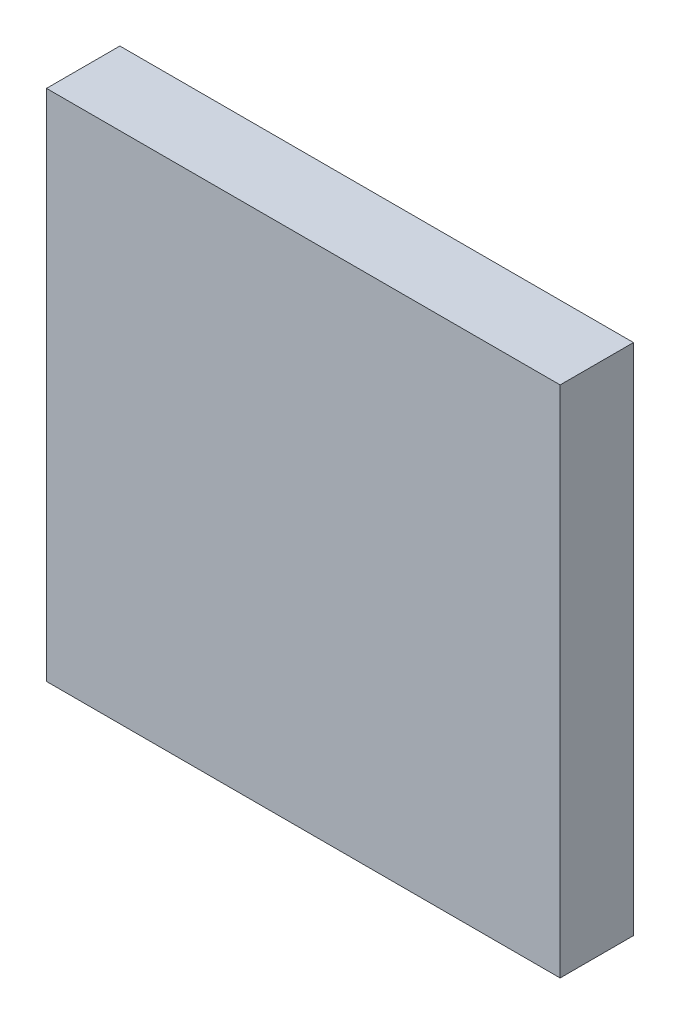
SolidWorks part; units mm, degrees
ref_plane "Спереди" through (0, 0, 0) normal (0, 0, 1) x (1, 0, 0)
ref_plane "Сверху" through (0, 0, 0) normal (0, 1, 0) x (1, 0, 0)
ref_plane "Справа" through (0, 0, 0) normal (1, 0, 0) x (0, 0, -1)
sketch "Эскиз5" plane through (0, 0, 0) normal (0, 0, 1) x (1, 0, 0)
  line L1 (-35, -35) -> (35, -35)
  line L2 (-35, -35) -> (-35, 35)
  line L3 (-35, 35) -> (35, 35)
  line L4 (35, -35) -> (35, 35)
  line L5 (-35, -35) -> (35, 35) construction
  line L6 (-35, 35) -> (35, -35) construction
  point P0 (0, 0)
extrude "Бобышка-Вытянуть2" add sketch "Эскиз5" along normal blind 10 contours L2 L3 L4 L1
sketch "Эскиз9" plane through (0, 0, 10) normal (0, 0, 1) x (1, 0, 0)
  line L0 (-15.9693, -2.4457) -> (-15.2752, -2.3914)
  line L1 (-14.1689, -1.194) -> (-14.17, 0.0011)
  line L2 (-15.1833, 1.1854) -> (-16.1735, 1.3414)
  line L3 (-7.5117, 15.2981) -> (-6.354, 13.3333)
  line L4 (-4.52, 14.0613) -> (-5.009, 16.2935)
  line L5 (5.8666, 15.0526) -> (5.5666, 14.4244)
  line L6 (6.0505, 12.8676) -> (7.0859, 12.271)
  line L7 (8.6182, 12.5564) -> (9.2484, 13.336)
  line L8 (16.9601, -1.13) -> (14.724, -1.1639)
  line L9 (14.4375, -3.1163) -> (16.5652, -3.7935)
  line L10 (10.1027, -12.6069) -> (9.7086, -12.0331)
  line L11 (8.1185, -11.6737) -> (7.0841, -12.2721)
  line L12 (6.5651, -13.7418) -> (6.9251, -14.6773)
  line L13 (-9.4469, -14.0923) -> (-8.37, -12.1694)
  line L14 (-9.9175, -10.9451) -> (-11.5447, -12.4356)
  line L15 (-30, -30) -> (30, -30)
  line L16 (30, -30) -> (30, 30)
  line L17 (30, 30) -> (-30, 30)
  line L18 (-30, 30) -> (-30, -30)
  ellipse E0 centre (-0.0001, 0.0435) end of major axis (-0.0001, 12.5436) minor radius 12.5001
  spline S0 degree 3 poles (3, -26) (3, -24.3431) (1.6569, -23) (0, -23) knots 0 0 0 0 0.2 0.2 0.2 0.2
  spline S1 degree 3 poles (0, -23) (-1.6568, -23) (-3, -24.3431) (-3, -26) knots 0.2 0.2 0.2 0.2 0.4 0.4 0.4 0.4
  spline S2 degree 3 poles (-3, -26) (-3, -27.6568) (-1.6569, -29) (0, -29) knots 0.4 0.4 0.4 0.4 0.6 0.6 0.6 0.6
  spline S3 degree 3 poles (0, -29) (1.6568, -29) (3, -27.6569) (3, -26) knots 0.6 0.6 0.6 0.6 1 1 1 1
  spline S4 degree 3 poles (-23, 0) (-23, 1.6569) (-24.3431, 3) (-26, 3) knots 0 0 0 0 0.2 0.2 0.2 0.2
  spline S5 degree 3 poles (-26, 3) (-27.6568, 3) (-29, 1.6569) (-29, 0) knots 0.2 0.2 0.2 0.2 0.4 0.4 0.4 0.4
  spline S6 degree 3 poles (-29, 0) (-29, -1.6568) (-27.6569, -3) (-26, -3) knots 0.4 0.4 0.4 0.4 0.6 0.6 0.6 0.6
  spline S7 degree 3 poles (-26, -3) (-24.3432, -3) (-23, -1.6569) (-23, 0) knots 0.6 0.6 0.6 0.6 1 1 1 1
  spline S8 degree 3 poles (29, 0) (29, 1.6569) (27.6569, 3) (26, 3) knots 0 0 0 0 0.2 0.2 0.2 0.2
  spline S9 degree 3 poles (26, 3) (24.3432, 3) (23, 1.6569) (23, 0) knots 0.2 0.2 0.2 0.2 0.4 0.4 0.4 0.4
  spline S10 degree 3 poles (23, 0) (23, -1.6568) (24.3431, -3) (26, -3) knots 0.4 0.4 0.4 0.4 0.6 0.6 0.6 0.6
  spline S11 degree 3 poles (26, -3) (27.6568, -3) (29, -1.6569) (29, 0) knots 0.6 0.6 0.6 0.6 1 1 1 1
  spline S12 degree 3 poles (3, 26) (3, 27.6569) (1.6569, 29) (0, 29) knots 0 0 0 0 0.2 0.2 0.2 0.2
  spline S13 degree 3 poles (0, 29) (-1.6568, 29) (-3, 27.6569) (-3, 26) knots 0.2 0.2 0.2 0.2 0.4 0.4 0.4 0.4
  spline S14 degree 3 poles (-3, 26) (-3, 24.3432) (-1.6569, 23) (0, 23) knots 0.4 0.4 0.4 0.4 0.6 0.6 0.6 0.6
  spline S15 degree 3 poles (0, 23) (1.6568, 23) (3, 24.3431) (3, 26) knots 0.6 0.6 0.6 0.6 1 1 1 1
  spline S16 degree 3 poles (-16.7485, -2.8866) (-16.7849, -2.7489) (-16.7119, -2.6575) (-16.5914, -2.5899) knots 0 0 0 0 0.021277 0.021277 0.021277 0.021277
  spline S17 degree 3 poles (-16.5914, -2.5899) (-16.4679, -2.5206) (-16.1105, -2.4568) (-15.9693, -2.4457) knots 0.021277 0.021277 0.021277 0.021277 0.042553 0.042553 0.042553 0.042553
  spline S18 degree 3 poles (-15.2752, -2.3914) (-14.6503, -2.3424) (-14.1684, -1.8208) (-14.1689, -1.194) knots 0.06383 0.06383 0.06383 0.06383 0.085106 0.085106 0.085106 0.085106
  spline S19 degree 3 poles (-14.17, 0.0011) (-14.1705, 0.5913) (-14.6002, 1.0936) (-15.1833, 1.1854) knots 0.106383 0.106383 0.106383 0.106383 0.12766 0.12766 0.12766 0.12766
  spline S20 degree 3 poles (-16.1735, 1.3414) (-16.4381, 1.383) (-16.9337, 1.6001) (-16.9034, 1.8662) knots 0.148936 0.148936 0.148936 0.148936 0.170213 0.170213 0.170213 0.170213
  spline S21 degree 3 poles (-16.9034, 1.8662) (-16.2735, 7.7755) (-12.6158, 12.7801) (-7.5117, 15.2981) knots 0.170213 0.170213 0.170213 0.170213 0.191489 0.191489 0.191489 0.191489
  spline S22 degree 3 poles (-6.354, 13.3333) (-6.1017, 12.914) (-5.5831, 12.7389) (-5.1282, 12.9194) knots 0.212766 0.212766 0.212766 0.212766 0.234043 0.234043 0.234043 0.234043
  spline S23 degree 3 poles (-5.1282, 12.9194) (-4.6734, 13.1) (-4.416, 13.5832) (-4.52, 14.0613) knots 0.234043 0.234043 0.234043 0.234043 0.255319 0.255319 0.255319 0.255319
  spline S24 degree 3 poles (-5.009, 16.2935) (-3.4256, 16.781) (-1.7434, 17.0434) (0, 17.0434) knots 0.276596 0.276596 0.276596 0.276596 0.297872 0.297872 0.297872 0.297872
  spline S25 degree 3 poles (0, 17.0434) (2.06, 17.0434) (4.0345, 16.6769) (5.8617, 16.0058) knots 0.297872 0.297872 0.297872 0.297872 0.319149 0.319149 0.319149 0.319149
  spline S26 degree 3 poles (5.8617, 16.0058) (5.9953, 15.9584) (6.0613, 15.8415) (6.1155, 15.7106) knots 0.319149 0.319149 0.319149 0.319149 0.340426 0.340426 0.340426 0.340426
  spline S27 degree 3 poles (6.1155, 15.7106) (6.1697, 15.5797) (5.9276, 15.1805) (5.8666, 15.0526) knots 0.340426 0.340426 0.340426 0.340426 0.361702 0.361702 0.361702 0.361702
  spline S28 degree 3 poles (5.5666, 14.4244) (5.2966, 13.8588) (5.5074, 13.1805) (6.0505, 12.8676) knots 0.382979 0.382979 0.382979 0.382979 0.404255 0.404255 0.404255 0.404255
  spline S29 degree 3 poles (7.0859, 12.271) (7.5974, 11.9764) (8.2472, 12.0974) (8.6182, 12.5564) knots 0.425532 0.425532 0.425532 0.425532 0.446809 0.446809 0.446809 0.446809
  spline S30 degree 3 poles (9.2484, 13.336) (9.4155, 13.5426) (9.7733, 13.9496) (9.9892, 13.8005) knots 0.468085 0.468085 0.468085 0.468085 0.489362 0.489362 0.489362 0.489362
  spline S31 degree 3 poles (9.9892, 13.8005) (9.9897, 13.8002) (9.9901, 13.7998) (9.9906, 13.7995) knots 0.489362 0.489362 0.489362 0.489362 0.510638 0.510638 0.510638 0.510638
  spline S32 degree 3 poles (9.9906, 13.7995) (14.2385, 10.7091) (17, 5.6988) (17, 0.0434) knots 0.510638 0.510638 0.510638 0.510638 0.531915 0.531915 0.531915 0.531915
  spline S33 degree 3 poles (17, 0.0434) (17, -0.351) (16.9865, -0.7423) (16.9601, -1.13) knots 0.531915 0.531915 0.531915 0.531915 0.553191 0.553191 0.553191 0.553191
  spline S34 degree 3 poles (14.724, -1.1639) (14.2347, -1.1728) (13.8237, -1.5344) (13.7527, -2.0186) knots 0.574468 0.574468 0.574468 0.574468 0.595745 0.595745 0.595745 0.595745
  spline S35 degree 3 poles (13.7527, -2.0186) (13.6816, -2.5027) (13.9714, -2.9672) (14.4375, -3.1163) knots 0.595745 0.595745 0.595745 0.595745 0.617021 0.617021 0.617021 0.617021
  spline S36 degree 3 poles (16.5652, -3.7935) (15.7442, -7.3523) (13.8058, -10.484) (11.1395, -12.7989) knots 0.638298 0.638298 0.638298 0.638298 0.659574 0.659574 0.659574 0.659574
  spline S37 degree 3 poles (11.1395, -12.7989) (11.0317, -12.8908) (10.5897, -12.8381) (10.4494, -12.8196) knots 0.659574 0.659574 0.659574 0.659574 0.680851 0.680851 0.680851 0.680851
  spline S38 degree 3 poles (10.4494, -12.8196) (10.3089, -12.8011) (10.1829, -12.7237) (10.1027, -12.6069) knots 0.680851 0.680851 0.680851 0.680851 0.702128 0.702128 0.702128 0.702128
  spline S39 degree 3 poles (9.7086, -12.0331) (9.3538, -11.5163) (8.661, -11.3598) (8.1185, -11.6737) knots 0.723404 0.723404 0.723404 0.723404 0.744681 0.744681 0.744681 0.744681
  spline S40 degree 3 poles (7.0841, -12.2721) (6.5732, -12.5677) (6.3531, -13.1909) (6.5651, -13.7418) knots 0.765957 0.765957 0.765957 0.765957 0.787234 0.787234 0.787234 0.787234
  spline S41 degree 3 poles (6.9251, -14.6773) (7.021, -14.9265) (6.922, -15.4856) (6.6778, -15.5949) knots 0.808511 0.808511 0.808511 0.808511 0.829787 0.829787 0.829787 0.829787
  spline S42 degree 3 poles (6.6778, -15.5949) (4.6278, -16.4714) (2.3705, -16.9566) (0, -16.9566) knots 0.829787 0.829787 0.829787 0.829787 0.851064 0.851064 0.851064 0.851064
  spline S43 degree 3 poles (0, -16.9566) (-3.4958, -16.9566) (-6.7452, -15.9014) (-9.4469, -14.0923) knots 0.851064 0.851064 0.851064 0.851064 0.87234 0.87234 0.87234 0.87234
  spline S44 degree 3 poles (-8.37, -12.1694) (-8.133, -11.7413) (-8.2407, -11.2045) (-8.6244, -10.9009) knots 0.893617 0.893617 0.893617 0.893617 0.914894 0.914894 0.914894 0.914894
  spline S45 degree 3 poles (-8.6244, -10.9009) (-9.0082, -10.5972) (-9.5554, -10.6159) (-9.9175, -10.9451) knots 0.914894 0.914894 0.914894 0.914894 0.93617 0.93617 0.93617 0.93617
  spline S46 degree 3 poles (-11.5447, -12.4356) (-14.22, -9.9595) (-16.0977, -6.6335) (-16.7485, -2.8866) knots 0.957447 0.957447 0.957447 0.957447 1 1 1 1
sketch "Эскиз13" plane through (0, 0, 10) normal (0, 0, 1) x (1, 0, 0)
  line L0 (-8.5, 3.8388) -> (-8.5, -2.9703)
  line L1 (8.5, -2.9278) -> (8.5, 3.8388)
  spline S0 degree 3 poles (-3.7602, -6.2881) (-4.1456, -5.7125) (-4.7609, -5.3316) (-5.448, -5.2431) knots 0 0 0 0 0.333333 0.333333 0.333333 0.333333
  spline S1 degree 3 poles (-5.448, -5.2431) (-6.135, -5.1547) (-6.8268, -5.3675) (-7.3454, -5.8267) knots 0.333333 0.333333 0.333333 0.333333 1 1 1 1
  spline S2 degree 3 poles (-8.2703, 4.2595) (-8.4134, 4.1675) (-8.5, 4.009) (-8.5, 3.8388) knots 0 0 0 0 1 1 1 1
  spline S3 degree 3 poles (8.2703, 4.2595) (3.2319, 7.4966) (-3.2319, 7.4966) (-8.2703, 4.2595) knots 0 0 0 0 1 1 1 1
  spline S4 degree 3 poles (8.5, 3.8388) (8.5, 4.009) (8.4134, 4.1675) (8.2703, 4.2595) knots 0 0 0 0 1 1 1 1
  spline S5 degree 3 poles (-8.9672, -4.0581) (-8.6689, -3.7749) (-8.5, -3.3816) (-8.5, -2.9703) knots 0 0 0 0 1 1 1 1
  spline S6 degree 3 poles (-8.9672, -4.0581) (-9.4419, -4.5088) (-9.4678, -5.2568) (-9.0253, -5.7393) knots 0 0 0 0 0.333333 0.333333 0.333333 0.333333
  spline S7 degree 3 poles (-9.0253, -5.7393) (-8.5829, -6.2218) (-7.8355, -6.2607) (-7.3454, -5.8267) knots 0.333333 0.333333 0.333333 0.333333 1 1 1 1
  spline S8 degree 3 poles (8.5, -2.9278) (8.5, -3.3579) (8.6732, -3.77) (8.9805, -4.0709) knots 0 0 0 0 1 1 1 1
  spline S9 degree 3 poles (7.6987, -6.0438) (6.4648, -5.5547) (5.0779, -5.6352) (3.9089, -6.2639) knots 0 0 0 0 1 1 1 1
  spline S10 degree 3 poles (7.6987, -6.0438) (8.2299, -6.2544) (8.8358, -6.0612) (9.1472, -5.5821) knots 0 0 0 0 0.333333 0.333333 0.333333 0.333333
  spline S11 degree 3 poles (9.1472, -5.5821) (9.4585, -5.1029) (9.3888, -4.4707) (8.9805, -4.0709) knots 0.333333 0.333333 0.333333 0.333333 1 1 1 1
  spline S12 degree 3 poles (3.1792, -6.3186) (1.2825, -5.6394) (-0.8063, -5.741) (-2.6281, -6.6012) knots 0 0 0 0 1 1 1 1
  spline S13 degree 3 poles (-3.7602, -6.2881) (-3.5123, -6.6582) (-3.0309, -6.7914) (-2.6281, -6.6012) knots 0 0 0 0 1 1 1 1
  spline S14 degree 3 poles (3.1792, -6.3186) (3.4192, -6.4045) (3.6844, -6.3847) (3.9089, -6.2639) knots 0 0 0 0 1 1 1 1
sketch "Эскиз15" plane through (0, 0, 10) normal (0, 0, 1) x (1, 0, 0)
  line L0 (-8.5, 3.8389) -> (-8.5, -2.9702)
  line L1 (8.5, -2.9277) -> (8.5, 3.8389)
  line L2 (-12.5, -12.5) -> (12.5, -12.5)
  line L3 (12.5, -12.5) -> (12.5, 12.5)
  line L4 (12.5, 12.5) -> (-12.5, 12.5)
  line L5 (-12.5, 12.5) -> (-12.5, -12.5)
  spline S0 degree 3 poles (8, 2.6874) (8, 2.9636) (7.7761, 3.1874) (7.5, 3.1874) knots 0 0 0 0 0.2 0.2 0.2 0.2
  spline S1 degree 3 poles (7.5, 3.1874) (7.2239, 3.1874) (7, 2.9636) (7, 2.6874) knots 0.2 0.2 0.2 0.2 0.4 0.4 0.4 0.4
  spline S2 degree 3 poles (7, 2.6874) (7, 2.4113) (7.2239, 2.1874) (7.5, 2.1874) knots 0.4 0.4 0.4 0.4 0.6 0.6 0.6 0.6
  spline S3 degree 3 poles (7.5, 2.1874) (7.7761, 2.1874) (8, 2.4113) (8, 2.6874) knots 0.6 0.6 0.6 0.6 1 1 1 1
  spline S4 degree 3 poles (-4.6079, 1.1218) (-4.6079, 1.6188) (-5.0108, 2.0218) (-5.5079, 2.0218) knots 0 0 0 0 0.2 0.2 0.2 0.2
  spline S5 degree 3 poles (-5.5079, 2.0218) (-6.0049, 2.0218) (-6.4079, 1.6188) (-6.4079, 1.1218) knots 0.2 0.2 0.2 0.2 0.4 0.4 0.4 0.4
  spline S6 degree 3 poles (-6.4079, 1.1218) (-6.4079, 0.6247) (-6.0049, 0.2218) (-5.5079, 0.2218) knots 0.4 0.4 0.4 0.4 0.6 0.6 0.6 0.6
  spline S7 degree 3 poles (-5.5079, 0.2218) (-5.0108, 0.2218) (-4.6079, 0.6247) (-4.6079, 1.1218) knots 0.6 0.6 0.6 0.6 1 1 1 1
  spline S8 degree 3 poles (7.0549, -0.2908) (7.0549, 0.2063) (6.652, 0.6092) (6.1549, 0.6092) knots 0 0 0 0 0.2 0.2 0.2 0.2
  spline S9 degree 3 poles (6.1549, 0.6092) (5.6579, 0.6092) (5.2549, 0.2063) (5.2549, -0.2908) knots 0.2 0.2 0.2 0.2 0.4 0.4 0.4 0.4
  spline S10 degree 3 poles (5.2549, -0.2908) (5.2549, -0.7878) (5.6579, -1.1908) (6.1549, -1.1908) knots 0.4 0.4 0.4 0.4 0.6 0.6 0.6 0.6
  spline S11 degree 3 poles (6.1549, -1.1908) (6.652, -1.1908) (7.0549, -0.7878) (7.0549, -0.2908) knots 0.6 0.6 0.6 0.6 1 1 1 1
  spline S12 degree 3 poles (-7, 2.6874) (-7, 2.9636) (-7.2239, 3.1874) (-7.5, 3.1874) knots 0 0 0 0 0.2 0.2 0.2 0.2
  spline S13 degree 3 poles (-7.5, 3.1874) (-7.7761, 3.1874) (-8, 2.9636) (-8, 2.6874) knots 0.2 0.2 0.2 0.2 0.4 0.4 0.4 0.4
  spline S14 degree 3 poles (-8, 2.6874) (-8, 2.4113) (-7.7761, 2.1874) (-7.5, 2.1874) knots 0.4 0.4 0.4 0.4 0.6 0.6 0.6 0.6
  spline S15 degree 3 poles (-7.5, 2.1874) (-7.2239, 2.1874) (-7, 2.4113) (-7, 2.6874) knots 0.6 0.6 0.6 0.6 1 1 1 1
  spline S16 degree 3 poles (-7.5909, -4.9282) (-7.5909, -4.6244) (-7.8371, -4.3782) (-8.1409, -4.3782) knots 0 0 0 0 0.2 0.2 0.2 0.2
  spline S17 degree 3 poles (-8.1409, -4.3782) (-8.4447, -4.3782) (-8.6909, -4.6244) (-8.6909, -4.9282) knots 0.2 0.2 0.2 0.2 0.4 0.4 0.4 0.4
  spline S18 degree 3 poles (-8.6909, -4.9282) (-8.6909, -5.2319) (-8.4447, -5.4782) (-8.1409, -5.4782) knots 0.4 0.4 0.4 0.4 0.6 0.6 0.6 0.6
  spline S19 degree 3 poles (-8.1409, -5.4782) (-7.8371, -5.4782) (-7.5909, -5.2319) (-7.5909, -4.9282) knots 0.6 0.6 0.6 0.6 1 1 1 1
  spline S20 degree 3 poles (8.6909, -4.9282) (8.6909, -4.6244) (8.4447, -4.3782) (8.1409, -4.3782) knots 0 0 0 0 0.2 0.2 0.2 0.2
  spline S21 degree 3 poles (8.1409, -4.3782) (7.8371, -4.3782) (7.5909, -4.6244) (7.5909, -4.9282) knots 0.2 0.2 0.2 0.2 0.4 0.4 0.4 0.4
  spline S22 degree 3 poles (7.5909, -4.9282) (7.5909, -5.2319) (7.8371, -5.4782) (8.1409, -5.4782) knots 0.4 0.4 0.4 0.4 0.6 0.6 0.6 0.6
  spline S23 degree 3 poles (8.1409, -5.4782) (8.4447, -5.4782) (8.6909, -5.2319) (8.6909, -4.9282) knots 0.6 0.6 0.6 0.6 1 1 1 1
  spline S24 degree 3 poles (3.9826, -5.4712) (3.9826, -5.195) (3.7587, -4.9712) (3.4826, -4.9712) knots 0 0 0 0 0.2 0.2 0.2 0.2
  spline S25 degree 3 poles (3.4826, -4.9712) (3.2064, -4.9712) (2.9826, -5.195) (2.9826, -5.4712) knots 0.2 0.2 0.2 0.2 0.4 0.4 0.4 0.4
  spline S26 degree 3 poles (2.9826, -5.4712) (2.9826, -5.7473) (3.2064, -5.9712) (3.4826, -5.9712) knots 0.4 0.4 0.4 0.4 0.6 0.6 0.6 0.6
  spline S27 degree 3 poles (3.4826, -5.9712) (3.7587, -5.9712) (3.9826, -5.7473) (3.9826, -5.4712) knots 0.6 0.6 0.6 0.6 1 1 1 1
  spline S28 degree 3 poles (-2.5123, -5.7872) (-2.5123, -5.5111) (-2.7362, -5.2872) (-3.0123, -5.2872) knots 0 0 0 0 0.2 0.2 0.2 0.2
  spline S29 degree 3 poles (-3.0123, -5.2872) (-3.2885, -5.2872) (-3.5123, -5.5111) (-3.5123, -5.7872) knots 0.2 0.2 0.2 0.2 0.4 0.4 0.4 0.4
  spline S30 degree 3 poles (-3.5123, -5.7872) (-3.5123, -6.0634) (-3.2885, -6.2872) (-3.0123, -6.2872) knots 0.4 0.4 0.4 0.4 0.6 0.6 0.6 0.6
  spline S31 degree 3 poles (-3.0123, -6.2872) (-2.7362, -6.2872) (-2.5123, -6.0634) (-2.5123, -5.7872) knots 0.6 0.6 0.6 0.6 1 1 1 1
  spline S32 degree 3 poles (6.6049, -0.2908) (6.6049, -0.0422) (6.4034, 0.1592) (6.1549, 0.1592) knots 0 0 0 0 0.2 0.2 0.2 0.2
  spline S33 degree 3 poles (6.1549, 0.1592) (5.9064, 0.1592) (5.7049, -0.0422) (5.7049, -0.2908) knots 0.2 0.2 0.2 0.2 0.4 0.4 0.4 0.4
  spline S34 degree 3 poles (5.7049, -0.2908) (5.7049, -0.5393) (5.9064, -0.7408) (6.1549, -0.7408) knots 0.4 0.4 0.4 0.4 0.6 0.6 0.6 0.6
  spline S35 degree 3 poles (6.1549, -0.7408) (6.4034, -0.7408) (6.6049, -0.5393) (6.6049, -0.2908) knots 0.6 0.6 0.6 0.6 1 1 1 1
  spline S36 degree 3 poles (-5.0579, 1.1218) (-5.0579, 1.3703) (-5.2594, 1.5718) (-5.5079, 1.5718) knots 0 0 0 0 0.2 0.2 0.2 0.2
  spline S37 degree 3 poles (-5.5079, 1.5718) (-5.7564, 1.5718) (-5.9579, 1.3703) (-5.9579, 1.1218) knots 0.2 0.2 0.2 0.2 0.4 0.4 0.4 0.4
  spline S38 degree 3 poles (-5.9579, 1.1218) (-5.9579, 0.8733) (-5.7564, 0.6718) (-5.5079, 0.6718) knots 0.4 0.4 0.4 0.4 0.6 0.6 0.6 0.6
  spline S39 degree 3 poles (-5.5079, 0.6718) (-5.2594, 0.6718) (-5.0579, 0.8733) (-5.0579, 1.1218) knots 0.6 0.6 0.6 0.6 1 1 1 1
  spline S40 degree 3 poles (5.7898, -5.6368) (5.8728, -5.6949) (5.9715, -5.7264) (6.0728, -5.7271) knots 0 0 0 0 1 1 1 1
  spline S41 degree 3 poles (-5.4083, -5.2485) (-5.2964, -5.2648) (-5.1822, -5.2427) (-5.0845, -5.1857) knots 0 0 0 0 1 1 1 1
  spline S42 degree 3 poles (-3.7602, -6.288) (-4.1456, -5.7124) (-4.7609, -5.3315) (-5.448, -5.243) knots 0 0 0 0 0.333333 0.333333 0.333333 0.333333
  spline S43 degree 3 poles (-5.448, -5.243) (-6.135, -5.1546) (-6.8268, -5.3674) (-7.3454, -5.8266) knots 0.333333 0.333333 0.333333 0.333333 1 1 1 1
  spline S44 degree 3 poles (-8.2703, 4.2596) (-8.4134, 4.1676) (-8.5, 4.0091) (-8.5, 3.8389) knots 0 0 0 0 1 1 1 1
  spline S45 degree 3 poles (8.2703, 4.2596) (3.2319, 7.4967) (-3.2319, 7.4967) (-8.2703, 4.2596) knots 0 0 0 0 1 1 1 1
  spline S46 degree 3 poles (8.5, 3.8389) (8.5, 4.0091) (8.4134, 4.1676) (8.2703, 4.2596) knots 0 0 0 0 1 1 1 1
  spline S47 degree 3 poles (5.7898, -5.6368) (2.563, -3.3793) (-1.6818, -3.2032) (-5.0845, -5.1857) knots 0 0 0 0 1 1 1 1
  spline S48 degree 3 poles (-8.9672, -4.058) (-8.6689, -3.7748) (-8.5, -3.3815) (-8.5, -2.9702) knots 0 0 0 0 1 1 1 1
  spline S49 degree 3 poles (-8.9672, -4.058) (-9.4419, -4.5087) (-9.4678, -5.2567) (-9.0253, -5.7392) knots 0 0 0 0 0.333333 0.333333 0.333333 0.333333
  spline S50 degree 3 poles (-9.0253, -5.7392) (-8.5829, -6.2217) (-7.8355, -6.2606) (-7.3454, -5.8266) knots 0.333333 0.333333 0.333333 0.333333 1 1 1 1
  spline S51 degree 3 poles (8.5, -2.9277) (8.5, -3.3578) (8.6732, -3.7699) (8.9805, -4.0708) knots 0 0 0 0 1 1 1 1
  spline S52 degree 3 poles (7.6987, -6.0437) (6.4648, -5.5546) (5.0779, -5.6351) (3.9089, -6.2638) knots 0 0 0 0 1 1 1 1
  spline S53 degree 3 poles (7.6987, -6.0437) (8.2299, -6.2543) (8.8358, -6.0611) (9.1472, -5.582) knots 0 0 0 0 0.333333 0.333333 0.333333 0.333333
  spline S54 degree 3 poles (9.1472, -5.582) (9.4585, -5.1028) (9.3888, -4.4706) (8.9805, -4.0708) knots 0.333333 0.333333 0.333333 0.333333 1 1 1 1
  spline S55 degree 3 poles (3.1792, -6.3185) (1.2825, -5.6393) (-0.8063, -5.7409) (-2.6281, -6.6011) knots 0 0 0 0 1 1 1 1
  spline S56 degree 3 poles (-3.7602, -6.288) (-3.5123, -6.6581) (-3.0309, -6.7913) (-2.6281, -6.6011) knots 0 0 0 0 1 1 1 1
  spline S57 degree 3 poles (3.1792, -6.3185) (3.4192, -6.4044) (3.6844, -6.3846) (3.9089, -6.2638) knots 0 0 0 0 1 1 1 1
sketch "обнижение под перлаж" plane through (0, 0, 10) normal (0, 0, 1) x (1, 0, 0)
  ellipse E0 centre (0, -7.2674) end of major axis (6.1105, -7.2674) minor radius 3.5988
sketch "Платина" plane through (0, 0, 10) normal (0, 0, 1) x (1, 0, 0)
  line L0 (12.3202, 9.8119) -> (12.2227, 9.9331)
  line L1 (2.5, -10.2511) -> (2.5, -15.1183)
  line L2 (7.4454, 12.0481) -> (8.1376, 12.9446)
  line L3 (11.9295, 9) -> (9.0138, 9)
  line L4 (8.1828, -12.8608) -> (5.8429, -9.208)
  line L5 (6.6238, -9) -> (11.9295, -9)
  line L6 (2.5, 15.1183) -> (2.5, 13.3766)
  line L7 (-0.6426, 13.86) -> (0.5426, 13.86)
  line L8 (1.1426, 14.46) -> (1.1426, 15.1613)
  line L9 (-6.3695, 9.5643) -> (-6.5795, 9.5485)
  line L10 (-0.9887, -9.3998) -> (-1.9416, -7.3197)
  line L11 (-0.0126, 4.7745) -> (-0.0058, 4.7671)
  line L12 (-5.5717, -10.8712) -> (-5.5074, -10.8831)
  line L13 (-2.7325, 15.5111) -> (-2.8513, 15.4898)
  line L14 (-1.1426, 14.46) -> (-1.1426, 15.1613)
  circle A0 centre (10.4255, 9.7146) radius 0.3
  circle A1 centre (10.4255, 9.7146) radius 0.35
  circle A2 centre (-9.7185, -10.4218) radius 0.4
  circle A3 centre (-9.7185, -10.4218) radius 0.6
  circle A4 centre (-5.4971, -13.8489) radius 0.4
  circle A5 centre (-8.9636, -11.0777) radius 0.35
  circle A6 centre (9.7185, 10.4218) radius 0.6
  circle A7 centre (-8.9636, -11.0777) radius 0.3
  circle A8 centre (9.7185, 10.4218) radius 0.4
  circle A9 centre (-3.1235, -7.8611) radius 0.55
  circle A10 centre (-3.1235, -7.8611) radius 0.5
  circle A11 centre (-5.0761, 0) radius 1.1
  circle A12 centre (-13.4764, 3.3335) radius 0.45
  circle A13 centre (-13.7094, -2.1616) radius 0.45
  circle A14 centre (-13.8634, 0.5974) radius 0.45
  circle A15 centre (-13.8634, 0.5974) radius 0.3
  circle A16 centre (-13.7094, -2.1616) radius 0.4
  circle A17 centre (-13.4764, 3.3335) radius 0.4
  circle A18 centre (-9.2449, 11.6851) radius 0.4
  circle A19 centre (11.3, 7.5) radius 0.55
  circle A20 centre (11.3, -7.5) radius 0.55
  circle A21 centre (9.7344, 5.5079) radius 0.45
  circle A22 centre (8.3218, -6.1549) radius 0.45
  circle A23 centre (14.7421, 2.1638) radius 0.4
  circle A24 centre (11.3, -7.5) radius 0.5
  circle A25 centre (11.3, 7.5) radius 0.5
  circle A26 centre (9.7344, 5.5079) radius 0.3
  circle A27 centre (8.3218, -6.1549) radius 0.3
  circle A28 centre (-5.0761, 0) radius 0.45
  circle A29 centre (-5.0761, 0) radius 0.4
  circle A30 centre (3.78, -11.6) radius 0.45
  circle A31 centre (-1.9546, 8.9725) radius 0.45
  circle A32 centre (-3.78, 11.6) radius 0.4
  circle A33 centre (-3.78, 11.6) radius 0.45
  circle A34 centre (-4.7981, 13.3147) radius 0.45
  circle A35 centre (3.78, -11.6) radius 0.4
  circle A36 centre (-1.9546, 8.9725) radius 0.4
  circle A37 centre (-4.7981, 13.3147) radius 0.4
  circle A38 centre (3.6844, 8.1409) radius 0.53
  circle A39 centre (2.8254, 3.0123) radius 0.53
  circle A40 centre (3.1415, -3.4824) radius 0.53
  circle A41 centre (3.6844, -8.1409) radius 0.53
  circle A42 centre (3.1415, -3.4824) radius 0.5
  circle A43 centre (2.8254, 3.0123) radius 0.5
  circle A44 centre (3.6844, -8.1409) radius 0.5
  circle A45 centre (3.6844, 8.1409) radius 0.5
  arc A46 (12.4118, 9.3683) -> (11.799, 10.1292) centre (0, 0) ccw
  arc A47 (2.439, 15.3575) -> (1.2728, 15.4978) centre (0, 0) ccw
  arc A48 (-13.8027, -7.1616) -> (-10.9014, -11.0888) centre (0, 0) ccw
  arc A49 (8.4366, -13.0624) -> (12.4117, -9.3677) centre (0, 0) ccw
  arc A50 (10.1874, 11.7482) -> (8.3636, 13.1093) centre (0, 0) ccw
  arc A51 (12.2227, 9.9331) -> (1.6964, 15.6584) centre (0, 0) ccw
  arc A52 (-9.1597, -12.5659) -> (2.439, -15.3575) centre (0, 0) ccw
  arc A53 (1.5549, -8.6935) -> (0.785, -8.4089) centre (1.071, -8.8191) ccw
  arc A54 (2.5, -10.2511) -> (2.3119, -9.8603) centre (2, -10.2511) ccw
  arc A55 (-9.1597, -12.5659) -> (-10.9014, -11.0888) centre (-11.0926, -13.0796) ccw
  arc A56 (-12.767, -7.0116) -> (-13.7672, -7.0979) centre (-13.233, -7.4492) ccw
  arc A57 (-12.767, -7.0116) -> (-5.5717, -10.8712) centre (-3.084, 2.403) ccw
  arc A58 (-5.3691, -10.9581) -> (-1.8802, -11.4789) centre (-3.1235, -7.8611) ccw
  arc A59 (-1.8802, -11.4789) -> (-0.9887, -9.3998) centre (-2.3763, -10.0355) ccw
  arc A60 (-0.6012, -9.2216) -> (-0.8748, -9.7613) centre (-0.383, -9.6714) ccw
  arc A61 (-0.6012, -9.2216) -> (0.785, -8.4089) centre (-5.0761, 0) ccw
  arc A62 (-5.3691, -10.9581) -> (-5.5717, -10.8712) centre (-5.6626, -11.3629) ccw
  arc A63 (2.439, -15.3575) -> (2.5, -15.1183) centre (2, -15.1183) ccw
  arc A64 (-13.7672, -7.0979) -> (-13.8027, -7.1616) centre (-13.3494, -7.3726) ccw
  arc A65 (10.1874, 11.7482) -> (11.799, 10.1292) centre (12.1567, 12.097) ccw
  arc A66 (6.0738, 3.7488) -> (7.4632, 11.4151) centre (3.6844, 8.1409) ccw
  arc A67 (7.4454, 12.0481) -> (7.4632, 11.4151) centre (7.8411, 11.7425) ccw
  arc A68 (8.5293, 9.3764) -> (9.0138, 9) centre (9.0138, 9.5) ccw
  arc A69 (8.3636, 13.1093) -> (8.1376, 12.9446) centre (8.5334, 12.639) ccw
  arc A70 (11.9295, 9) -> (12.4118, 9.3683) centre (11.9295, 9.5) ccw
  arc A71 (6.6238, -9) -> (6.2027, -9.7697) centre (6.6238, -9.5) ccw
  arc A72 (12.4117, -9.3677) -> (11.9295, -9) centre (11.9295, -9.5) ccw
  arc A73 (8.1828, -12.8608) -> (8.4366, -13.0624) centre (8.6038, -12.5912) ccw
  arc A74 (2.1531, 12.9006) -> (2.5, 13.3766) centre (2, 13.3766) ccw
  arc A75 (-0.6426, 13.86) -> (-0.8081, 13.1169) centre (-0.6426, 13.47) ccw
  arc A76 (2.1531, 12.9006) -> (-0.7378, 10.4741) centre (3.6844, 8.1409) ccw
  arc A77 (0.5671, 12.4555) -> (1.117, 12.4314) centre (0.8603, 12.8605) ccw
  arc A78 (0.5426, 13.86) -> (1.1426, 14.46) centre (0.5426, 14.46) ccw
  arc A79 (1.2728, 15.4978) -> (1.1426, 15.1613) centre (1.6426, 15.1613) ccw
  arc A80 (2.5, 15.1183) -> (2.439, 15.3575) centre (2, 15.1183) ccw
  arc A81 (-7.0932, 10.1997) -> (-6.5795, 9.5485) centre (-6.617, 10.0471) ccw
  arc A82 (-6.0923, 10.1429) -> (-6.3468, 10.7247) centre (-6.5734, 10.279) ccw
  arc A83 (-6.3695, 9.5643) -> (-6.1876, 9.7286) centre (-6.3845, 9.7637) ccw
  arc A84 (-5.612, 11.2339) -> (-0.5457, 4.9099) centre (-1.9546, 8.9725) ccw
  arc A85 (-6.3468, 10.7247) -> (-7.0716, 10.2777) centre (-6.4873, 10.1414) ccw
  arc A86 (-7.8732, 9.5197) -> (-7.0716, 10.2777) centre (-8.0455, 10.5047) ccw
  arc A87 (0.4324, -5.6985) -> (-0.2788, -5.6343) centre (0.0454, -6.015) ccw
  arc A88 (1.6904, -7.2114) -> (1.4753, -6.5604) centre (1.2372, -7.0001) ccw
  arc A89 (-1.9416, -7.3197) -> (-1.9622, -7.2769) centre (-3.1235, -7.8611) ccw
  arc A90 (-1.7409, -6.6058) -> (-1.9622, -7.2769) centre (-1.5156, -7.0521) ccw
  arc A91 (-0.2801, -2.7456) -> (1.4753, -6.5604) centre (3.1415, -3.4824) ccw
  arc A92 (-2.5221, -6.9453) -> (-0.2788, -5.6343) centre (-5.0761, 0) ccw
  arc A93 (-12.4906, -4.5249) -> (-11.6206, -3.4539) centre (-12.2839, -3.804) ccw
  arc A94 (-13.294, -3.176) -> (-13.4339, -4.0149) centre (-13.1045, -3.6387) ccw
  arc A95 (-13.294, -3.176) -> (-12.6266, -1.9908) centre (-13.7094, -2.1616) ccw
  arc A96 (-12.4086, 3.0694) -> (-12.6266, -1.9908) centre (0, 0) ccw
  arc A97 (-12.4086, 3.0694) -> (-12.9816, 4.3159) centre (-13.4764, 3.3335) ccw
  arc A98 (-13.2216, 4.8947) -> (-12.9816, 4.3159) centre (-12.7656, 4.7446) ccw
  arc A99 (-7.8732, 9.5197) -> (-13.2216, 4.8947) centre (-6.6881, 2.7443) ccw
  arc A100 (-6.5006, 7.2616) -> (-11.6206, -3.4539) centre (-5.0761, 0) ccw
  arc A101 (-13.3852, -4.0569) -> (-11.2448, -4.5599) centre (-11.7995, -2.1148) ccw
  arc A102 (-6.5006, 7.2616) -> (-6.1133, 7.8794) centre (-6.5969, 7.7522) ccw
  arc A103 (-13.4339, -4.0149) -> (-13.3852, -4.0569) centre (-10.4129, -0.5655) ccw
  arc A104 (-1.2717, -8.7821) -> (-2.4697, -8.5503) centre (-1.9535, -9.0945) ccw
  arc A105 (-2.8425, -6.9536) -> (-2.4697, -8.5503) centre (-3.1235, -7.8611) ccw
  arc A106 (-2.8425, -6.9536) -> (-2.5221, -6.9453) centre (-2.6946, -6.476) ccw
  arc A107 (-4.3028, -9.861) -> (-4.6898, -7.9124) centre (-13.084, -10.592) ccw
  arc A108 (-4.6898, -7.9124) -> (-5.6008, -7.2173) centre (-5.6424, -8.2165) ccw
  arc A109 (-10.7557, -4.7208) -> (-11.2448, -4.5599) centre (-11.1341, -5.0475) ccw
  arc A110 (-0.0126, 4.7745) -> (-0.5457, 4.9099) centre (-0.3819, 4.4375) ccw
  arc A111 (0.0824, 4.2272) -> (-0.0058, 4.7671) centre (-0.3748, 4.4297) ccw
  arc A112 (1.0574, 5.436) -> (-0.1603, 2.719) centre (2.8254, 3.0123) ccw
  arc A113 (-0.5383, 2.1847) -> (-0.1603, 2.719) centre (-0.6579, 2.6702) ccw
  arc A114 (-0.5383, 2.1847) -> (-0.6291, -2.1603) centre (0, 0) ccw
  arc A115 (-5.5074, -10.8831) -> (-4.3028, -9.861) centre (-5.2932, -9.9147) ccw
  arc A116 (-10.7557, -4.7208) -> (-5.6008, -7.2173) centre (-5.2873, 0) ccw
  arc A117 (-0.2801, -2.7456) -> (-0.6291, -2.1603) centre (-0.7689, -2.6403) ccw
  arc A118 (-15.296, -2.8563) -> (-15.5588, 0.228) centre (-16.2412, -1.3835) ccw
  arc A119 (-15.7416, 0.514) -> (-15.5588, 0.228) centre (-15.4418, 0.5042) ccw
  arc A120 (-15.5207, 1.1114) -> (-15.7275, 0.8421) centre (-15.4279, 0.8261) ccw
  arc A121 (-15.5207, 1.1114) -> (-14.9936, 4.1616) centre (-16.0619, 2.7756) ccw
  arc A122 (-15.098, 4.4846) -> (-14.9936, 4.1616) centre (-14.8104, 4.3992) ccw
  arc A123 (-15.0279, 4.5471) -> (-15.1077, 4.359) centre (-14.9095, 4.3858) ccw
  arc A124 (-14.6619, 4.639) -> (-12.956, 5.577) centre (-14.4341, 6.2451) ccw
  arc A125 (-13.3852, -4.0569) -> (-15.0699, -3.3705) centre (-15.3458, -6.4583) ccw
  arc A126 (-15.37, -3.2347) -> (-15.0699, -3.3705) centre (-15.0254, -2.8725) ccw
  arc A127 (-15.4285, -3.0519) -> (-15.37, -3.2347) centre (-15.2322, -3.0898) ccw
  arc A128 (-15.296, -2.8563) -> (-15.4279, -3.1692) centre (-15.134, -3.1088) ccw
  arc A129 (-14.6619, 4.639) -> (-15.0279, 4.5471) centre (-14.732, 4.144) ccw
  arc A130 (-5.612, 11.2339) -> (-5.7556, 11.91) centre (-6.0372, 11.4968) ccw
  arc A131 (-6.4878, 13.5014) -> (-7.2138, 14.0008) centre (-6.9848, 13.5564) ccw
  arc A132 (-6.4878, 13.5014) -> (-5.1181, 11.6451) centre (-4.7981, 13.3147) ccw
  arc A133 (5.4708, -6.0947) -> (5.4112, -6.7777) centre (5.8036, -6.4679) ccw
  arc A134 (5.4708, -6.0947) -> (3.9942, -0.0879) centre (3.1415, -3.4824) ccw
  arc A135 (3.9942, 0.2494) -> (3.9942, -0.0879) centre (4.1787, 0.0807) ccw
  arc A136 (3.9942, 0.2494) -> (5.2866, 4.7276) centre (2.8254, 3.0123) ccw
  arc A137 (6.0738, 3.7488) -> (5.8145, 3.2671) centre (6.3127, 3.3096) ccw
  arc A138 (5.7863, -8.7906) -> (5.8429, -9.208) centre (6.264, -8.9383) ccw
  arc A139 (1.6904, -7.2114) -> (5.4112, -6.7777) centre (3.6844, -8.1409) ccw
  arc A140 (-2.8513, 15.4898) -> (-2.9574, 15.1516) centre (-2.8159, 15.2929) ccw
  arc A141 (-2.5522, 15.4522) -> (-2.7325, 15.5111) centre (-2.6971, 15.3143) ccw
  arc A142 (-1.7022, 13.4831) -> (-2.5522, 15.4522) centre (-4.7981, 13.3147) ccw
  arc A143 (-1.9042, 13.2722) -> (-1.7022, 13.4831) centre (-1.9019, 13.4722) ccw
  arc A144 (-2.2017, 13.461) -> (-1.9999, 13.2723) centre (-2.002, 13.4723) ccw
  arc A145 (-2.2017, 13.461) -> (-2.9574, 15.1516) centre (-4.7981, 13.3147) ccw
  arc A146 (0.5671, 12.4555) -> (-2.8467, 13.179) centre (-1.9546, 8.9725) ccw
  arc A147 (-3.0981, 13.3147) -> (-2.8467, 13.179) centre (-2.9059, 13.37) ccw
  arc A148 (-3.1791, 12.7964) -> (-3.616, 14.5364) centre (-4.7981, 13.3147) ccw
  arc A149 (-3.3754, 15.3841) -> (-3.616, 14.5364) centre (-3.2683, 14.8957) ccw
  arc A150 (-2.8513, 15.4898) -> (12.3202, 9.8119) centre (0, 0) ccw
  arc A151 (-1.1426, 15.1613) -> (-1.6964, 15.6584) centre (-1.6426, 15.1613) ccw
  arc A152 (-1.1426, 14.46) -> (-0.5426, 13.86) centre (-0.5426, 14.46) ccw
  arc A153 (-1.6964, 15.6584) -> (-2.7325, 15.5111) centre (0, 0) ccw
  arc A154 (-3.1791, 12.7964) -> (-3.0619, 12.2959) centre (-2.7029, 12.6439) ccw
  arc A155 (-1.3839, 10.2509) -> (-0.7378, 10.4741) centre (-1.18, 10.7075) ccw
  arc A156 (-1.3839, 10.2509) -> (-1.7772, 7.5838) centre (-1.9546, 8.9725) ccw
  arc A157 (-1.2231, 7.1836) -> (-1.7772, 7.5838) centre (-1.7138, 7.0878) ccw
  arc A158 (-4.7348, 11.3027) -> (-5.1181, 11.6451) centre (-5.2122, 11.154) ccw
  arc A159 (-4.7348, 11.3027) -> (-3.0619, 12.2959) centre (-3.78, 11.6) ccw
  arc A160 (-1.2231, 7.1836) -> (-0.0126, 4.7745) centre (3.6844, 8.1409) ccw
  arc A161 (5.0447, 7.5087) -> (2.1924, 7.9864) centre (3.6844, 8.1409) ccw
  arc A162 (1.0574, 5.436) -> (2.1924, 7.9864) centre (-0.5927, 7.6981) ccw
  arc A163 (5.0447, 7.5087) -> (5.2866, 4.7276) centre (7.5838, 6.3285) ccw
  arc A164 (-0.6291, -2.1603) -> (-0.5383, 2.1847) centre (0, 0) ccw
  spline S0 degree 3 poles (11.799, 10.1292) (11.833, 10.1237) (11.8667, 10.1191) (11.9002, 10.1155) knots 0 0 0 0 1 1 1 1
  spline S1 degree 3 poles (12.2227, 9.9331) (12.1797, 9.9867) (12.1265, 10.0297) (12.0148, 10.0901) (11.9565, 10.1078) (11.9002, 10.1155) knots 0 0 0 0 0.5 0.5 1 1 1 1
  spline S2 degree 3 poles (12.4118, 9.3683) (12.4298, 9.4342) (12.4355, 9.5076) (12.409, 9.6619) (12.375, 9.7434) (12.3202, 9.8119) knots 0 0 0 0 0.5 0.5 1 1 1 1
  spline S3 degree 3 poles (2.439, 15.3575) (2.4063, 15.4176) (2.3596, 15.4744) (2.2335, 15.5673) (2.1526, 15.6025) (2.0656, 15.614) knots 0 0 0 0 0.5 0.5 1 1 1 1
  spline S4 degree 3 poles (1.6964, 15.6584) (1.6091, 15.6678) (1.5233, 15.6533) (1.3773, 15.5924) (1.3188, 15.5484) (1.2728, 15.4978) knots 0 0 0 0 0.5 0.5 1 1 1 1
  spline S5 degree 3 poles (-10.9014, -11.0888) (-10.9357, -11.0855) (-10.9696, -11.0831) (-11.0033, -11.0816) knots 0 0 0 0 1 1 1 1
  spline S6 degree 3 poles (-11.341, -10.9291) (-11.2932, -10.9786) (-11.2364, -11.0166) (-11.1197, -11.0667) (-11.0601, -11.0791) (-11.0033, -11.0816) knots 0 0 0 0 0.5 0.5 1 1 1 1
  spline S7 degree 3 poles (-13.8027, -7.1616) (-13.8315, -7.2236) (-13.8495, -7.2949) (-13.8493, -7.4515) (-13.8295, -7.5375) (-13.7871, -7.6144) knots 0 0 0 0 0.5 0.5 1 1 1 1
  spline S8 degree 3 poles (12.3206, -9.8115) (12.3753, -9.7428) (12.4089, -9.6625) (12.4357, -9.5066) (12.4298, -9.4337) (12.4117, -9.3677) knots 0 0 0 0 0.5 0.5 1 1 1 1
  spline S9 degree 3 poles (8.4366, -13.0624) (8.5011, -13.0852) (8.5738, -13.0964) (8.7297, -13.0813) (8.8134, -13.0535) (8.8859, -13.004) knots 0 0 0 0 0.5 0.5 1 1 1 1
  spline S10 degree 3 poles (8.8131, 13.0534) (8.7404, 13.1025) (8.6577, 13.1297) (8.5002, 13.1441) (8.4279, 13.1325) (8.3636, 13.1093) knots 0 0 0 0 0.5 0.5 1 1 1 1
  spline S11 degree 3 poles (10.1721, 11.8491) (10.1651, 11.9055) (10.1481, 11.9636) (10.089, 12.0761) (10.0464, 12.13) (9.9932, 12.1736) knots 0 0 0 0 0.5 0.5 1 1 1 1
  spline S12 degree 3 poles (10.1721, 11.8491) (10.1763, 11.8157) (10.1814, 11.7821) (10.1874, 11.7482) knots 0 0 0 0 1 1 1 1
  spline S13 degree 3 poles (2.0656, -15.614) (2.1526, -15.6025) (2.2325, -15.5679) (2.3599, -15.4742) (2.4063, -15.4176) (2.439, -15.3575) knots 0 0 0 0 0.5 0.5 1 1 1 1
  spline S14 degree 3 poles (-9.136, -12.6652) (-9.1242, -12.7208) (-9.1024, -12.7773) (-9.034, -12.8844) (-8.987, -12.9345) (-8.9303, -12.9735) knots 0 0 0 0 0.5 0.5 1 1 1 1
  spline S15 degree 3 poles (-9.136, -12.6652) (-9.143, -12.6324) (-9.1508, -12.5993) (-9.1597, -12.5659) knots 0 0 0 0 1 1 1 1
sketch "обнижение под платину" plane through (0, 0, 10) normal (0, 0, 1) x (1, 0, 0)
  line L1 (-1.1425, 14.458) -> (-1.1425, 15.1592)
  line L2 (1.1427, 14.458) -> (1.1427, 15.1592)
  line L3 (-0.5425, 13.858) -> (0.5427, 13.858)
  spline S5 degree 3 poles (-1.6963, 15.6563) (-2.043, 15.6188) (-2.3883, 15.5697) (-2.7317, 15.5092) knots 0 0 0 0 1 1 1 1
  spline S6 degree 3 poles (-1.1425, 14.458) (-1.1425, 14.2988) (-1.0792, 14.1462) (-0.9667, 14.0337) knots 0 0 0 0 0.333333 0.333333 0.333333 0.333333
  spline S7 degree 3 poles (-0.9667, 14.0337) (-0.8542, 13.9212) (-0.7016, 13.858) (-0.5425, 13.858) knots 0.333333 0.333333 0.333333 0.333333 1 1 1 1
  spline S8 degree 3 poles (-1.1425, 15.1592) (-1.1425, 15.3012) (-1.2028, 15.4365) (-1.3085, 15.5313) knots 0 0 0 0 0.333333 0.333333 0.333333 0.333333
  spline S9 degree 3 poles (-1.3085, 15.5313) (-1.4142, 15.6262) (-1.5552, 15.6716) (-1.6963, 15.6563) knots 0.333333 0.333333 0.333333 0.333333 1 1 1 1
  spline S10 degree 3 poles (-2.7317, 15.5092) (-9.6978, 14.2443) (-14.9639, 8.4868) (-15.6035, 1.4358) knots 0 0 0 0 0.2 0.2 0.2 0.2
  spline S11 degree 3 poles (-15.6035, 1.4358) (-16.2631, -5.6135) (-12.1379, -12.2364) (-5.5202, -14.7529) knots 0.2 0.2 0.2 0.2 0.4 0.4 0.4 0.4
  spline S12 degree 3 poles (-5.5202, -14.7529) (1.1106, -17.2344) (8.5824, -14.9865) (12.7432, -9.2581) knots 0.4 0.4 0.4 0.4 0.6 0.6 0.6 0.6
  spline S13 degree 3 poles (12.7432, -9.2581) (16.9041, -3.5298) (16.7312, 4.2709) (12.3208, 9.8094) knots 0.6 0.6 0.6 0.6 1 1 1 1
  spline S16 degree 3 poles (1.2729, 15.4958) (1.1891, 15.4037) (1.1427, 15.2837) (1.1427, 15.1592) knots 0 0 0 0 1 1 1 1
  spline S17 degree 3 poles (0.5427, 13.858) (0.874, 13.858) (1.1427, 14.1266) (1.1427, 14.458) knots 0 0 0 0 1 1 1 1
  spline S18 degree 3 poles (12.3208, 9.8094) (9.688, 13.082) (5.87, 15.1832) (1.6965, 15.6563) knots 0 0 0 0 1 1 1 1
  spline S19 degree 3 poles (1.6965, 15.6563) (1.6092, 15.6658) (1.5234, 15.6512) (1.4504, 15.6208) knots 0 0 0 0 0.333333 0.333333 0.333333 0.333333
  spline S20 degree 3 poles (1.4504, 15.6208) (1.3774, 15.5904) (1.3189, 15.5464) (1.2729, 15.4958) knots 0.333333 0.333333 0.333333 0.333333 1 1 1 1
sketch "пипка-остров" plane through (0, 0, 10) normal (0, 0, 1) x (1, 0, 0)
  spline S2 degree 3 poles (-0.6292, -2.1624) (0.2793, -2.427) (1.2563, -2.0948) (1.8153, -1.3313) knots 0 0 0 0 0.25 0.25 0.25 0.25
  spline S3 degree 3 poles (1.8153, -1.3313) (2.3743, -0.5678) (2.3959, 0.4638) (1.8693, 1.25) knots 0.25 0.25 0.25 0.25 0.5 0.5 0.5 0.5
  spline S4 degree 3 poles (1.8693, 1.25) (1.3427, 2.0362) (0.3804, 2.4089) (-0.5383, 2.1825) knots 0.5 0.5 0.5 0.5 1 1 1 1
  spline S14 degree 3 poles (-0.5383, 2.1825) (-1.5266, 1.939) (-2.2283, 1.0625) (-2.2496, 0.0449) knots 0 0 0 0 0.333333 0.333333 0.333333 0.333333
  spline S15 degree 3 poles (-2.2496, 0.0449) (-2.2709, -0.9727) (-1.6064, -1.8778) (-0.6292, -2.1624) knots 0.333333 0.333333 0.333333 0.333333 1 1 1 1
sketch "Эскиз24" [suppressed] plane through (0, 0, 10) normal (0, 0, 1) x (1, 0, 0)
  arc A0 (10.1874, 11.7482) -> (11.799, 10.1292) centre (12.1567, 12.097) ccw construction
  ellipse E0 centre (10.7393, 10.686) end of major axis (12.6794, 12.6172) minor radius 2.6434
  ellipse E1 centre (-10.119, 11.0435) end of major axis (-11.9999, 13.0962) minor radius 2.2561
  ellipse E2 centre (-10.9014, -11.0888) end of major axis (-12.9041, -12.7834) minor radius 1.4551
  ellipse E3 centre (11.753, -11.0888) end of major axis (12.8895, -13.6427) minor radius 2.2348
sketch "Эскиз25" plane through (0, 0, 10) normal (0, 0, 1) x (1, 0, 0)
  circle A0 centre (0, 0) radius 14.2175
  circle A2 centre (0, 0) radius 12.5175
  circle A3 centre (0, 0) radius 10.8175
  circle A4 centre (0, 0) radius 9.1175
  circle A5 centre (0, 0) radius 7.4175
  circle A6 centre (0, 0) radius 5.7175
  circle A7 centre (0, 0) radius 4.0175
  circle A8 centre (0, 0) radius 2.3175
  dimension "D1" = 1.7
  dimension "D2" = 1.7
  dimension "D3" = 1.7
  dimension "D4" = 1.7
  dimension "D5" = 1.7
  dimension "D6" = 1.7
  dimension "D7" = 1.7
sketch "1_2,95" plane through (0, 0, 10) normal (0, 0, 1) x (1, 0, 0)
  circle A0 centre (12.0784, 7.5) radius 1.475
  circle A1 centre (0, 0) radius 14.2175 construction
  circle A2 centre (12.8546, 6.0743) radius 1.475
  circle A3 centre (13.4632, 4.5694) radius 1.475
  circle A4 centre (13.8963, 3.0049) radius 1.475
  circle A5 centre (14.1483, 1.4013) radius 1.475
  circle A6 centre (14.2158, -0.2207) radius 1.475
  circle A7 centre (14.098, -1.8397) radius 1.475
  circle A8 centre (13.7964, -3.4348) radius 1.475
  circle A9 centre (13.3149, -4.985) radius 1.475
  circle A10 centre (12.6599, -6.4703) radius 1.475
  circle A56 centre (10.0219, 7.5) radius 1.475
  circle A57 centre (0, 0) radius 12.5175 construction
  circle A58 centre (10.9321, 6.0973) radius 1.475
  circle A59 centre (11.6472, 4.5858) radius 1.475
  circle A60 centre (12.1545, 2.9924) radius 1.475
  circle A61 centre (12.445, 1.3457) radius 1.475
  circle A62 centre (12.5133, -0.3251) radius 1.475
  circle A63 centre (12.3583, -1.99) radius 1.475
  circle A64 centre (11.9828, -3.6195) radius 1.475
  circle A65 centre (11.3935, -5.1843) radius 1.475
  circle A66 centre (10.6008, -6.6567) radius 1.475
  circle A105 centre (8.8447, 2.2135) radius 1.475
  circle A106 centre (9.0978, 0.5986) radius 1.475
  circle A107 centre (9.3884, 5.3736) radius 1.475
  circle A108 centre (0, 0) radius 10.8175 construction
  circle A109 centre (10.0987, 3.8775) radius 1.475
  circle A110 centre (10.5722, 2.2905) radius 1.475
  circle A111 centre (10.798, 0.6498) radius 1.475
  circle A112 centre (10.7706, -1.0061) radius 1.475
  circle A113 centre (10.4908, -2.6384) radius 1.475
  circle A114 centre (9.9651, -4.2089) radius 1.475
  circle A115 centre (9.2058, -5.6807) radius 1.475
  circle A116 centre (8.2308, -7.0194) radius 1.475
  circle A149 centre (8.3074, 3.7572) radius 1.475
  circle A150 centre (0, 0) radius 9.1175 construction
  circle A151 centre (9.0585, -1.0355) radius 1.475
  circle A152 centre (8.728, -2.6363) radius 1.475
  circle A153 centre (8.1171, -4.1524) radius 1.475
  circle A154 centre (7.2452, -5.535) radius 1.475
  circle A155 centre (6.1404, -6.7397) radius 1.475
  circle A183 centre (6.9312, 2.6415) radius 1.475
  circle A184 centre (0, 0) radius 7.4175 construction
  circle A185 centre (7.3552, 0.9751) radius 1.475
  circle A186 centre (7.3834, -0.7442) radius 1.475
  circle A187 centre (7.0144, -2.4236) radius 1.475
  circle A211 centre (11.1447, 8.8279) radius 1.475 [skipped]
  circle A212 centre (10.0658, 10.0408) radius 1.475 [skipped]
  circle A213 centre (8.8556, 11.1228) radius 1.475 [skipped]
  circle A214 centre (7.53, 12.0597) radius 1.475 [skipped]
  circle A215 centre (6.1062, 12.8395) radius 1.475 [skipped]
  circle A216 centre (4.6028, 13.4518) radius 1.475 [skipped]
  circle A217 centre (3.0394, 13.8888) radius 1.475 [skipped]
  circle A218 centre (1.4364, 14.1448) radius 1.475 [skipped]
  circle A219 centre (-0.1854, 14.2163) radius 1.475 [skipped]
  circle A220 centre (8.9328, 8.7689) radius 1.475 [skipped]
  circle A221 centre (7.6843, 9.8812) radius 1.475 [skipped]
  circle A222 centre (6.2987, 10.8173) radius 1.475 [skipped]
  circle A223 centre (4.8007, 11.5603) radius 1.475 [skipped]
  circle A224 centre (3.217, 12.097) radius 1.475 [skipped]
  circle A225 centre (1.5759, 12.4179) radius 1.475 [skipped]
  circle A226 centre (7.3295, 7.9559) radius 1.475 [skipped]
  circle A227 centre (6.0292, 8.9815) radius 1.475 [skipped]
  circle A228 centre (4.5875, 9.7966) radius 1.475 [skipped]
  circle A229 centre (3.0383, 10.3821) radius 1.475 [skipped]
  circle A230 centre (1.4179, 10.7242) radius 1.475 [skipped]
  circle A231 centre (8.4581, 6.7438) radius 1.475 [skipped]
  circle A232 centre (7.503, 5.1802) radius 1.475 [skipped]
  circle A233 centre (6.1344, 4.1653) radius 1.475 [skipped]
  circle A234 centre (6.4574, 6.4366) radius 1.475 [skipped]
  circle A235 centre (5.0076, 5.4642) radius 1.475 [skipped]
  circle A236 centre (5.2044, 7.4862) radius 1.475 [skipped]
  circle A237 centre (3.6117, 6.4682) radius 1.475 [skipped]
  circle A238 centre (3.784, 8.2952) radius 1.475 [skipped]
  circle A239 centre (2.0218, 7.1232) radius 1.475 [skipped]
  circle A240 centre (2.242, 8.8375) radius 1.475 [skipped]
  circle A241 centre (0.3237, 7.394) radius 1.475 [skipped]
  circle A242 centre (0.628, 9.0958) radius 1.475 [skipped]
  circle A243 centre (-1.8047, 14.1025) radius 1.475 [skipped]
  circle A244 centre (-3.4005, 13.8049) radius 1.475 [skipped]
  circle A245 centre (-4.952, 13.3272) radius 1.475 [skipped]
  circle A246 centre (-6.4389, 12.6759) radius 1.475 [skipped]
  circle A247 centre (-7.8419, 11.8593) radius 1.475 [skipped]
  circle A248 centre (-9.1426, 10.8881) radius 1.475 [skipped]
  circle A249 centre (-10.3241, 9.7749) radius 1.475 [skipped]
  circle A250 centre (-11.3711, 8.5344) radius 1.475 [skipped]
  circle A251 centre (-12.2698, 7.1825) radius 1.475 [skipped]
  circle A252 centre (-13.0086, 5.737) radius 1.475 [skipped]
  circle A253 centre (-13.5778, 4.2168) radius 1.475 [skipped]
  circle A254 centre (-13.97, 2.6415) radius 1.475 [skipped]
  circle A255 centre (-14.18, 1.0319) radius 1.475 [skipped]
  circle A256 centre (-14.2052, -0.5913) radius 1.475 [skipped]
  circle A257 centre (-14.0452, -2.2067) radius 1.475 [skipped]
  circle A258 centre (-13.7021, -3.7933) radius 1.475 [skipped]
  circle A259 centre (-13.1804, -5.3305) radius 1.475 [skipped]
  circle A260 centre (-12.4868, -6.7982) radius 1.475 [skipped]
  circle A261 centre (-11.6305, -8.1773) radius 1.475 [skipped]
  circle A262 centre (-10.6226, -9.4498) radius 1.475 [skipped]
  circle A263 centre (-9.4761, -10.5991) radius 1.475 [skipped]
  circle A264 centre (-8.2062, -11.6102) radius 1.475 [skipped]
  circle A265 centre (-6.8292, -12.4699) radius 1.475 [skipped]
  circle A266 centre (-5.3632, -13.1671) radius 1.475 [skipped]
  circle A267 centre (10.8653, -9.1696) radius 1.475 [skipped]
  circle A268 centre (9.7493, -10.3484) radius 1.475 [skipped]
  circle A269 centre (8.5061, -11.3923) radius 1.475 [skipped]
  circle A270 centre (7.152, -12.2876) radius 1.475 [skipped]
  circle A271 centre (5.7047, -13.0228) radius 1.475 [skipped]
  circle A272 centre (4.1831, -13.5882) radius 1.475 [skipped]
  circle A273 centre (2.6069, -13.9765) radius 1.475 [skipped]
  circle A274 centre (0.9967, -14.1825) radius 1.475 [skipped]
  circle A275 centre (-0.6265, -14.2037) radius 1.475 [skipped]
  circle A276 centre (-2.2415, -14.0397) radius 1.475 [skipped]
  circle A277 centre (-3.8273, -13.6927) radius 1.475 [skipped]
  circle A278 centre (8.4655, -9.2208) radius 1.475 [skipped]
  circle A279 centre (7.1609, -10.2669) radius 1.475 [skipped]
  circle A280 centre (5.7286, -11.1297) radius 1.475 [skipped]
  circle A281 centre (4.194, -11.794) radius 1.475 [skipped]
  circle A282 centre (2.5846, -12.2478) radius 1.475 [skipped]
  circle A283 centre (0.9291, -12.483) radius 1.475 [skipped]
  circle A284 centre (-0.743, -12.4954) radius 1.475 [skipped]
  circle A285 centre (-2.4019, -12.2849) radius 1.475 [skipped]
  circle A286 centre (-4.0178, -11.8552) radius 1.475 [skipped]
  circle A287 centre (-5.5621, -11.2139) radius 1.475 [skipped]
  circle A288 centre (-7.0072, -10.3724) radius 1.475 [skipped]
  circle A289 centre (-8.3272, -9.3459) radius 1.475 [skipped]
  circle A290 centre (-0.0933, 12.5172) radius 1.475 [skipped]
  circle A291 centre (-1.7608, 12.393) radius 1.475 [skipped]
  circle A292 centre (-3.3969, 12.0478) radius 1.475 [skipped]
  circle A293 centre (-4.9724, 11.4875) radius 1.475 [skipped]
  circle A294 centre (-6.4592, 10.7223) radius 1.475 [skipped]
  circle A295 centre (-7.8307, 9.7657) radius 1.475 [skipped]
  circle A296 centre (-9.0625, 8.6348) radius 1.475 [skipped]
  circle A297 centre (-10.1325, 7.3498) radius 1.475 [skipped]
  circle A298 centre (-11.0217, 5.9337) radius 1.475 [skipped]
  circle A299 centre (-11.7143, 4.4117) radius 1.475 [skipped]
  circle A300 centre (-12.1978, 2.811) radius 1.475 [skipped]
  circle A301 centre (-12.4636, 1.1601) radius 1.475 [skipped]
  circle A302 centre (-12.507, -0.5115) radius 1.475 [skipped]
  circle A303 centre (-12.3273, -2.1739) radius 1.475 [skipped]
  circle A304 centre (-11.9275, -3.7976) radius 1.475 [skipped]
  circle A305 centre (-11.3149, -5.3535) radius 1.475 [skipped]
  circle A306 centre (-10.5004, -6.8139) radius 1.475 [skipped]
  circle A307 centre (-9.4985, -8.1526) radius 1.475 [skipped]
  circle A308 centre (5.7293, -9.1757) radius 1.475 [skipped]
  circle A309 centre (4.2615, -9.9427) radius 1.475 [skipped]
  circle A310 centre (2.6938, -10.4767) radius 1.475 [skipped]
  circle A311 centre (1.063, -10.7651) radius 1.475 [skipped]
  circle A312 centre (-0.5928, -10.8012) radius 1.475 [skipped]
  circle A313 centre (-2.2346, -10.5842) radius 1.475 [skipped]
  circle A314 centre (4.8383, -7.7278) radius 1.475 [skipped]
  circle A315 centre (3.8223, -6.3572) radius 1.475 [skipped]
  circle A316 centre (5.1845, -5.3079) radius 1.475 [skipped]
  circle A317 centre (-6.699, -8.4936) radius 1.475 [skipped]
  circle A318 centre (-7.917, -7.3715) radius 1.475 [skipped]
  circle A319 centre (-8.9495, -6.0766) radius 1.475 [skipped]
  circle A320 centre (-9.7722, -4.6392) radius 1.475 [skipped]
  circle A321 centre (-10.3659, -3.0931) radius 1.475 [skipped]
  circle A322 centre (-10.7165, -1.4745) radius 1.475 [skipped]
  circle A323 centre (-10.816, 0.1786) radius 1.475 [skipped]
  circle A324 centre (-10.662, 1.8276) radius 1.475 [skipped]
  circle A325 centre (-10.2581, 3.4337) radius 1.475 [skipped]
  circle A326 centre (-9.6137, 4.9594) radius 1.475 [skipped]
  circle A327 centre (-8.744, 6.3688) radius 1.475 [skipped]
  circle A328 centre (-7.6693, 7.6289) radius 1.475 [skipped]
  circle A329 centre (-6.4149, 8.7102) radius 1.475 [skipped]
  circle A330 centre (-5.0101, 9.5873) radius 1.475 [skipped]
  circle A331 centre (-3.4879, 10.2398) radius 1.475 [skipped]
  circle A332 centre (-1.8839, 10.6522) radius 1.475 [skipped]
  circle A333 centre (-0.2358, 10.8149) radius 1.475 [skipped]
  circle A334 centre (-3.0252, -8.601) radius 1.475 [skipped]
  circle A335 centre (-4.5124, -7.9226) radius 1.475 [skipped]
  circle A336 centre (-5.8545, -6.9896) radius 1.475 [skipped]
  circle A337 centre (-7.0084, -5.8319) radius 1.475 [skipped]
  circle A338 centre (-7.9371, -4.4868) radius 1.475 [skipped]
  circle A339 centre (-8.6107, -2.9974) radius 1.475 [skipped]
  circle A340 centre (-9.0075, -1.4117) radius 1.475 [skipped]
  circle A341 centre (-9.1149, 0.2193) radius 1.475 [skipped]
  circle A342 centre (-8.9292, 1.8433) radius 1.475 [skipped]
  circle A343 centre (-8.4566, 3.408) radius 1.475 [skipped]
  circle A344 centre (-7.7122, 4.8633) radius 1.475 [skipped]
  circle A345 centre (-6.7199, 6.1622) radius 1.475 [skipped]
  circle A346 centre (-5.5116, 7.263) radius 1.475 [skipped]
  circle A347 centre (-4.1261, 8.1304) radius 1.475 [skipped]
  circle A348 centre (-2.6081, 8.7365) radius 1.475 [skipped]
  circle A349 centre (-1.0062, 9.0618) radius 1.475 [skipped]
  circle A350 centre (-1.1514, -7.3187) radius 1.475 [skipped]
  circle A351 centre (-2.8066, -6.8526) radius 1.475 [skipped]
  circle A352 centre (-4.3097, -6.0175) radius 1.475 [skipped]
  circle A353 centre (-5.5796, -4.8582) radius 1.475 [skipped]
  circle A354 centre (-6.5479, -3.4372) radius 1.475 [skipped]
  circle A355 centre (-7.1625, -1.8313) radius 1.475 [skipped]
  circle A356 centre (-7.3901, -0.1269) radius 1.475 [skipped]
  circle A357 centre (-7.2186, 1.584) radius 1.475 [skipped]
  circle A358 centre (-6.6571, 3.2092) radius 1.475 [skipped]
  circle A359 centre (-5.7359, 4.6612) radius 1.475 [skipped]
  circle A360 centre (-4.5048, 5.8616) radius 1.475 [skipped]
  circle A361 centre (-3.0299, 6.7457) radius 1.475 [skipped]
  circle A362 centre (-1.391, 7.2658) radius 1.475 [skipped]
  circle A363 centre (-3.8241, -10.119) radius 1.475 [skipped]
  circle A364 centre (-5.324, -9.4167) radius 1.475 [skipped]
  circle A365 centre (3.3807, -8.4676) radius 1.475 [skipped]
  circle A366 centre (1.8144, -8.9351) radius 1.475 [skipped]
  circle A367 centre (0.1899, -9.1155) radius 1.475 [skipped]
  circle A368 centre (-1.4408, -9.0029) radius 1.475 [skipped]
  circle A369 centre (2.2548, -7.0641) radius 1.475 [skipped]
  circle A370 centre (0.5666, -7.3905) radius 1.475 [skipped]
  circle A371 centre (6.268, -3.9727) radius 1.475 [skipped]
  circle A372 centre (5.5052, 0.189) radius 1.475
  circle A373 centre (9.619, -8.0102) radius 1.475 [skipped]
  circle A374 centre (7.0628, -8.1936) radius 1.475 [skipped]
  circle A375 centre (7.1443, -7.5124) radius 1.475
  circle A376 centre (11.8398, -7.8713) radius 1.475 [skipped]
  circle A377 centre (12.1545, -7.5124) radius 1.475
  circle A378 centre (9.7644, -7.5124) radius 1.475
  dimension "D1" = 55
  dimension "D2" = 47
  dimension "D3" = 41
  dimension "D4" = 35
  dimension "D5" = 27
sketch "верха 2.95" plane through (0, 0, 10) normal (0, 0, 1) x (1, 0, 0)
  circle A0 centre (1.7596, -14.1082) radius 1.475
  circle A1 centre (0, 0) radius 14.2175 construction
  circle A2 centre (0.1375, -14.214) radius 1.475
  circle A3 centre (-1.4861, -14.1341) radius 1.475
  circle A4 centre (-3.09, -13.8697) radius 1.475
  circle A5 centre (-4.6534, -13.4242) radius 1.475
  circle A6 centre (-6.1557, -12.8034) radius 1.475
  circle A7 centre (-7.5775, -12.0154) radius 1.475
  circle A8 centre (-8.9002, -11.0704) radius 1.475
  circle A9 centre (-10.1066, -9.9809) radius 1.475
  circle A10 centre (-11.1809, -8.7609) radius 1.475
  circle A11 centre (-12.1091, -7.4264) radius 1.475
  circle A56 centre (3.3591, -13.8182) radius 1.475
  circle A57 centre (4.9151, -13.3478) radius 1.475
  circle A58 centre (6.4073, -12.7031) radius 1.475
  circle A59 centre (11.3673, -8.5808) radius 1.475
  circle A60 centre (12.2741, -7.2317) radius 1.475
  circle A61 centre (13.0212, -5.788) radius 1.475
  circle A62 centre (13.5988, -4.2685) radius 1.475
  circle A63 centre (13.9995, -2.6931) radius 1.475
  circle A64 centre (14.218, -1.0823) radius 1.475
  circle A65 centre (14.2514, 0.5429) radius 1.475
  circle A66 centre (14.0994, 2.1614) radius 1.475
  circle A67 centre (13.7639, 3.7519) radius 1.475
  circle A68 centre (13.2492, 5.2939) radius 1.475
  circle A69 centre (12.5621, 6.7671) radius 1.475
  circle A70 centre (11.7116, 8.1524) radius 1.475
  circle A71 centre (6.9254, 12.4752) radius 1.475
  circle A72 centre (5.461, 13.1808) radius 1.475
  circle A73 centre (3.9256, 13.7148) radius 1.475
  circle A74 centre (2.3394, 14.0703) radius 1.475
  circle A75 centre (0.723, 14.2427) radius 1.475
  circle A76 centre (-13.7741, 3.532) radius 1.475
  circle A77 centre (-13.2841, 5.082) radius 1.475
  circle A78 centre (-12.6207, 6.566) radius 1.475
  circle A79 centre (-11.7924, 7.9647) radius 1.475
  circle A80 centre (-10.8101, 9.2599) radius 1.475
  circle A81 centre (-9.6865, 10.4346) radius 1.475
  circle A82 centre (-8.4363, 11.4737) radius 1.475
  circle A83 centre (-7.0759, 12.3634) radius 1.475
  circle A84 centre (-5.6229, 13.0923) radius 1.475
  circle A85 centre (-4.0963, 13.6507) radius 1.475
  circle A86 centre (-2.5159, 14.0316) radius 1.475
  circle A87 centre (-0.9025, 14.2297) radius 1.475
  circle A88 centre (-13.9068, -2.916) radius 1.475
  circle A89 centre (-14.151, -1.3088) radius 1.475
  circle A90 centre (-14.2104, 0.3156) radius 1.475
  circle A91 centre (-14.0842, 1.9363) radius 1.475
  circle A92 centre (-13.481, -4.4848) radius 1.475
  circle A93 centre (-12.8792, -5.9948) radius 1.475
  circle A94 centre (10.3126, -9.8178) radius 1.475
  circle A95 centre (9.1238, -10.9265) radius 1.475
  circle A96 centre (7.8164, -11.8925) radius 1.475
  circle A97 centre (8.2999, 11.6073) radius 1.475
  circle A98 centre (9.5665, 10.5884) radius 1.475
  circle A99 centre (10.7087, 9.4317) radius 1.475
  circle A100 centre (1.1621, -12.4634) radius 1.475
  circle A101 centre (0, 0) radius 12.5175 construction
  circle A102 centre (-0.5459, -12.5056) radius 1.475
  circle A103 centre (-2.2436, -12.3148) radius 1.475
  circle A104 centre (-3.8996, -11.8946) radius 1.475
  circle A105 centre (-5.4829, -11.2528) radius 1.475
  circle A147 centre (5.4829, 11.2528) radius 1.475
  circle A148 centre (6.9641, 10.4014) radius 1.475
  circle A149 centre (8.3156, 9.3562) radius 1.475
  circle A150 centre (9.5121, 8.1368) radius 1.475
  circle A151 centre (10.5315, 6.7658) radius 1.475
  circle A152 centre (11.3547, 5.2687) radius 1.475
  circle A153 centre (11.9663, 3.6735) radius 1.475
  circle A154 centre (12.3551, 2.0099) radius 1.475
  circle A155 centre (12.5137, 0.3088) radius 1.475
  circle A156 centre (12.4392, -1.398) radius 1.475
  circle A157 centre (12.133, -3.0788) radius 1.475
  circle A158 centre (11.6007, -4.7022) radius 1.475
  circle A159 centre (10.8524, -6.2381) radius 1.475
  circle A160 centre (9.9019, -7.6577) radius 1.475
  circle A161 centre (8.7669, -8.9347) radius 1.475
  circle A162 centre (7.4687, -10.0452) radius 1.475
  circle A163 centre (6.0313, -10.9686) radius 1.475
  circle A164 centre (4.4816, -11.6877) radius 1.475
  circle A165 centre (-12.3551, -2.0099) radius 1.475
  circle A166 centre (-12.5137, -0.3088) radius 1.475
  circle A167 centre (-12.4392, 1.398) radius 1.475
  circle A168 centre (-12.133, 3.0788) radius 1.475
  circle A169 centre (-11.6007, 4.7022) radius 1.475
  circle A170 centre (-10.8524, 6.2381) radius 1.475
  circle A171 centre (-9.9019, 7.6577) radius 1.475
  circle A172 centre (-8.7669, 8.9347) radius 1.475
  circle A173 centre (-7.4687, 10.0452) radius 1.475
  circle A174 centre (-6.0313, 10.9686) radius 1.475
  circle A175 centre (-4.4816, 11.6877) radius 1.475
  circle A176 centre (-2.8483, 12.1891) radius 1.475
  circle A177 centre (-1.1621, 12.4634) radius 1.475
  circle A178 centre (0.5459, 12.5056) radius 1.475
  circle A179 centre (2.2436, 12.3148) radius 1.475
  circle A180 centre (3.8996, 11.8946) radius 1.475
  circle A181 centre (-11.9663, -3.6735) radius 1.475
  circle A182 centre (-11.3547, -5.2687) radius 1.475
  circle A183 centre (-10.5315, -6.7658) radius 1.475
  circle A184 centre (-9.5121, -8.1368) radius 1.475
  circle A185 centre (-8.3156, -9.3562) radius 1.475
  circle A186 centre (-6.9641, -10.4014) radius 1.475
  circle A187 centre (2.8483, -12.1891) radius 1.475
  circle A188 centre (1.7596, -10.6734) radius 1.475
  circle A189 centre (0, 0) radius 10.8175 construction
  circle A190 centre (0, -10.8175) radius 1.475
  circle A191 centre (0.2845, -9.1131) radius 1.475
  circle A192 centre (0, 0) radius 9.1175 construction
  circle A193 centre (0.4544, -7.4036) radius 1.475
  circle A194 centre (0, 0) radius 7.4175 construction
  circle A195 centre (-0.7731, -7.3771) radius 1.475
  circle A196 centre (0, -6.7662) radius 1.475
  circle A197 centre (8.6069, -11.3163) radius 1.475
  circle A200 centre (7.5545, -9.9809) radius 1.475
  circle A201 centre (10.9128, -9.1131) radius 1.475
  circle A202 centre (9.8367, -10.2653) radius 1.475
  circle A203 centre (9.7185, 10.4218) radius 1.475
  circle A204 centre (10.9128, 9.1131) radius 1.475
  circle A205 centre (8.2032, 11.6123) radius 1.475
  circle A206 centre (-8.4826, 9.2051) radius 1.475
  circle A207 centre (-7.1873, 8.0846) radius 1.475
  circle A208 centre (-9.6712, 7.947) radius 1.475
  circle A209 centre (-10.7145, 6.472) radius 1.475
  circle A210 centre (-11.5275, 4.8789) radius 1.475
  circle A211 centre (-12.1091, 3.1714) radius 1.475
  circle A212 centre (-12.5084, -0.4777) radius 1.475
  circle A213 centre (-12.4466, 1.3304) radius 1.475
  circle A214 centre (-12.2973, -2.3376) radius 1.475
  circle A215 centre (-12.4466, -3.9735) radius 1.475
  dimension "D1" = 55
  dimension "D2" = 46
sketch "Эскиз27" plane through (0, 0, 10) normal (0, 0, 1) x (1, 0, 0)
  circle A0 centre (-5.0761, 0) radius 5.8
  circle A1 centre (-5.0761, 0) radius 4.1
  circle A2 centre (-5.0761, 0) radius 2.4
  dimension "D1" = 1.7
  dimension "D2" = 1.7
sketch "2,95 под лунным колесом" plane through (0, 0, 10) normal (0, 0, 1) x (1, 0, 0)
  circle A0 centre (-6.0655, 5.715) radius 1.475
  circle A1 centre (-5.0761, 0) radius 5.8 construction
  circle A2 centre (-4.337, 5.7527) radius 1.475
  circle A3 centre (-2.6742, 5.2793) radius 1.475
  circle A4 centre (-1.2248, 4.3368) radius 1.475
  circle A10 centre (-1.705, -4.7197) radius 1.475
  circle A11 centre (-3.246, -5.5037) radius 1.475
  circle A12 centre (-4.9495, -5.7986) radius 1.475
  circle A13 centre (-6.6643, -5.5783) radius 1.475
  circle A14 centre (-8.238, -4.8623) radius 1.475
  circle A15 centre (-9.5307, -3.7143) radius 1.475
  circle A16 centre (-10.4276, -2.2363) radius 1.475
  circle A17 centre (-10.849, -0.5595) radius 1.475
  circle A18 centre (-10.7575, 1.1669) radius 1.475
  circle A19 centre (-10.1611, 2.7897) radius 1.475
  circle A20 centre (-9.1129, 4.1646) radius 1.475
  circle A21 centre (-7.7061, 5.1695) radius 1.475
  circle A22 centre (0.549, 1.4137) radius 1.475
  circle A23 centre (0.7158, -0.3071) radius 1.475
  circle A24 centre (-0.1176, 3.0089) radius 1.475
  circle A25 centre (0.3679, -2.0007) radius 1.475
  circle A26 centre (-0.4636, -3.5164) radius 1.475
  circle A27 centre (-2.8153, 3.4203) radius 1.475
  circle A28 centre (-5.0761, 0) radius 4.1 construction
  circle A29 centre (-1.5551, 2.1007) radius 1.475
  circle A32 centre (-2.2446, -2.9652) radius 1.475
  circle A33 centre (-3.8116, -3.9001) radius 1.475
  circle A34 centre (-5.629, -4.0625) radius 1.475
  circle A35 centre (-7.3369, -3.4203) radius 1.475
  circle A36 centre (-8.5971, -2.1007) radius 1.475
  circle A37 centre (-9.1598, -0.365) radius 1.475
  circle A38 centre (-8.9138, 1.443) radius 1.475
  circle A39 centre (-7.9076, 2.9652) radius 1.475
  circle A40 centre (-6.3406, 3.9001) radius 1.475
  circle A41 centre (-4.5232, 4.0625) radius 1.475
  circle A42 centre (-0.9924, 0.365) radius 1.475
  circle A43 centre (-1.2384, -1.443) radius 1.475
  circle A44 centre (-3.3249, 1.6411) radius 1.475
  circle A45 centre (-5.0761, 0) radius 2.4 construction
  circle A46 centre (-2.7012, -0.3459) radius 1.475
  circle A47 centre (-3.8658, -2.0725) radius 1.475
  circle A48 centre (-5.9418, -2.2384) radius 1.475
  circle A49 centre (-7.3659, -0.7188) radius 1.475
  circle A50 centre (-7.0658, 1.3421) radius 1.475
  circle A51 centre (-5.2673, 2.3924) radius 1.475
  point P47 (-5.0761, 0)
  point P78 (-5.0761, 0)
  point P95 (-5.0761, 0)
  dimension "D1" = 21
  dimension "D2" = 14
  dimension "D3" = 7
sketch "карман под съем моста" plane through (0, 0, 10) normal (0, 0, 1) x (1, 0, 0)
  line L0 (-13.7619, 0) -> (13.4181, 0) construction
  line L1 (-13.7619, 1) -> (13.4181, 1)
  line L2 (-13.7619, -1) -> (13.4181, -1)
  arc A0 (-13.7619, 1) -> (-13.7619, -1) centre (-13.7619, 0) ccw
  arc A1 (13.4181, -1) -> (13.4181, 1) centre (13.4181, 0) ccw
  point P3 (-0.1719, 0)
sketch "Эскиз28" plane through (0, 0, 10) normal (0, 0, 1) x (1, 0, 0)
  line L1 (-15.2666, -8.0853) -> (15.2666, -8.0853)
  line L2 (-15.2666, -8.0853) -> (-15.2666, 8.0853)
  line L3 (-15.2666, 8.0853) -> (15.2666, 8.0853)
  line L4 (15.2666, -8.0853) -> (15.2666, 8.0853)
  line L5 (-15.2666, -8.0853) -> (15.2666, 8.0853) construction
  line L6 (-15.2666, 8.0853) -> (15.2666, -8.0853) construction
  point P0 (0, 0)
sketch "острова" plane through (0, 0, 10) normal (0, 0, 1) x (1, 0, 0)
  spline S0 degree 2 poles (-8.5, -2.0317) (-8.5, -2.5998) (-8.5, -2.9703) knots 0 0 0 1 1 1
  spline S1 degree 3 poles (-5.4691, 5.3435) (-5.4628, 5.5492) (-5.3311, 5.73) (-5.1372, 5.7991) knots 0 0 0 0 1 1 1 1
  spline S2 degree 3 poles (-8.3317, 4.2129) (-8.1698, 4.2866) (-7.9808, 4.2686) (-7.8357, 4.1657) knots 0 0 0 0 1 1 1 1
  spline S3 degree 3 poles (-8.3317, 4.2129) (-8.3126, 4.2298) (-8.2921, 4.2455) (-8.2703, 4.2595) knots 0 0 0 0 1 1 1 1
  spline S4 degree 3 poles (-8.0243, -2.5311) (-8.2907, -2.5182) (-8.5, -2.2984) (-8.5, -2.0317) knots 0 0 0 0 1 1 1 1
  spline S5 degree 3 poles (-8.0243, -2.5311) (-6.7965, -2.5908) (-5.8123, -3.5687) (-5.7445, -4.7961) knots 0 0 0 0 1 1 1 1
  spline S6 degree 3 poles (-5.3331, -5.2608) (-5.5614, -5.2201) (-5.7318, -5.0277) (-5.7445, -4.7961) knots 0 0 0 0 1 1 1 1
  spline S7 degree 3 poles (6.4277, -5.7438) (6.8591, -5.781) (7.2875, -5.8808) (7.6987, -6.0438) knots 0 0 0 0 1 1 1 1
  spline S8 degree 3 poles (6.962, -5.1523) (6.9912, -5.3061) (6.9468, -5.4647) (6.8418, -5.5808) knots 0 0 0 0 0.333333 0.333333 0.333333 0.333333
  spline S9 degree 3 poles (6.8418, -5.5808) (6.7369, -5.697) (6.5837, -5.7573) (6.4277, -5.7438) knots 0.333333 0.333333 0.333333 0.333333 1 1 1 1
  spline S10 degree 3 poles (6.962, -5.1523) (6.898, -4.8155) (6.9811, -4.4674) (7.1904, -4.1958) knots 0 0 0 0 0.333333 0.333333 0.333333 0.333333
  spline S11 degree 3 poles (7.1904, -4.1958) (7.3997, -3.9242) (7.7151, -3.7551) (8.0571, -3.7312) knots 0.333333 0.333333 0.333333 0.333333 1 1 1 1
  spline S12 degree 3 poles (8.5169, -3.1599) (8.5371, -3.2976) (8.499, -3.4375) (8.4117, -3.5459) knots 0 0 0 0 0.333333 0.333333 0.333333 0.333333
  spline S13 degree 3 poles (8.4117, -3.5459) (8.3245, -3.6543) (8.196, -3.7215) (8.0571, -3.7312) knots 0.333333 0.333333 0.333333 0.333333 1 1 1 1
  spline S14 degree 3 poles (8.9805, -4.0709) (8.729, -3.8247) (8.5673, -3.504) (8.5169, -3.1599) knots 0 0 0 0 1 1 1 1
  spline S15 degree 3 poles (8.2703, 4.2595) (8.2921, 4.2455) (8.3126, 4.2298) (8.3317, 4.2129) knots 0 0 0 0 1 1 1 1
  spline S16 degree 3 poles (7.8357, 4.1657) (7.9808, 4.2686) (8.1698, 4.2866) (8.3317, 4.2129) knots 0 0 0 0 1 1 1 1
  spline S17 degree 3 poles (7.8357, 4.1657) (7.3848, 3.8462) (6.7948, 3.8005) (6.3001, 4.0467) knots 0 0 0 0 0.333333 0.333333 0.333333 0.333333
  spline S18 degree 3 poles (6.3001, 4.0467) (5.8054, 4.2929) (5.4861, 4.7912) (5.4691, 5.3435) knots 0.333333 0.333333 0.333333 0.333333 1 1 1 1
  spline S19 degree 3 poles (5.1372, 5.7991) (5.3311, 5.73) (5.4628, 5.5492) (5.4691, 5.3435) knots 0 0 0 0 1 1 1 1
  spline S20 degree 3 poles (-8.2703, 4.2595) (-7.2743, 4.8994) (-6.2227, 5.4129) (-5.1372, 5.7991) knots 0 0 0 0 1 1 1 1
  spline S21 degree 3 poles (5.1372, 5.7991) (6.2227, 5.4129) (7.2744, 4.8994) (8.2703, 4.2595) knots 0 0 0 0 1 1 1 1
  spline S22 degree 3 poles (-7.3454, -5.8267) (-6.8268, -5.3675) (-6.135, -5.1547) (-5.448, -5.2431) knots 0 0 0 0 0.333333 0.333333 0.333333 0.333333
  spline S23 degree 3 poles (-5.448, -5.2431) (-5.4095, -5.2481) (-5.3711, -5.254) (-5.3331, -5.2608) knots 0.333333 0.333333 0.333333 0.333333 1 1 1 1
  spline S24 degree 3 poles (-5.4691, 5.3435) (-5.4861, 4.7912) (-5.8054, 4.2929) (-6.3001, 4.0467) knots 0 0 0 0 0.333333 0.333333 0.333333 0.333333
  spline S25 degree 3 poles (-6.3001, 4.0467) (-6.7948, 3.8005) (-7.3848, 3.8462) (-7.8357, 4.1657) knots 0.333333 0.333333 0.333333 0.333333 1 1 1 1
  spline S26 degree 3 poles (-8.5, -2.9703) (-8.5, -3.3816) (-8.6689, -3.7749) (-8.9672, -4.0581) knots 0 0 0 0 1 1 1 1
  spline S27 degree 3 poles (8.9805, -4.0709) (9.3888, -4.4707) (9.4585, -5.1029) (9.1472, -5.5821) knots 0 0 0 0 0.333333 0.333333 0.333333 0.333333
  spline S28 degree 3 poles (9.1472, -5.5821) (8.8358, -6.0612) (8.2299, -6.2544) (7.6987, -6.0438) knots 0.333333 0.333333 0.333333 0.333333 1 1 1 1
  spline S29 degree 3 poles (-7.3454, -5.8267) (-7.8355, -6.2607) (-8.5829, -6.2218) (-9.0253, -5.7393) knots 0 0 0 0 0.333333 0.333333 0.333333 0.333333
  spline S30 degree 3 poles (-9.0253, -5.7393) (-9.4678, -5.2568) (-9.4419, -4.5088) (-8.9672, -4.0581) knots 0.333333 0.333333 0.333333 0.333333 1 1 1 1
sketch "Перлаж" plane through (0, 0, 10) normal (0, 0, 1) x (1, 0, 0)
  circle A0 centre (-3.5742, -6.0861) radius 1.45
  circle A1 centre (-1.8079, -5.4766) radius 1.45
  circle A2 centre (0.0493, -5.272) radius 1.45
  circle A3 centre (1.9059, -5.4823) radius 1.45
  circle A4 centre (3.6703, -6.0971) radius 1.45
  point P13 (0.0365, -13.6857)
  dimension "D1" = 5
